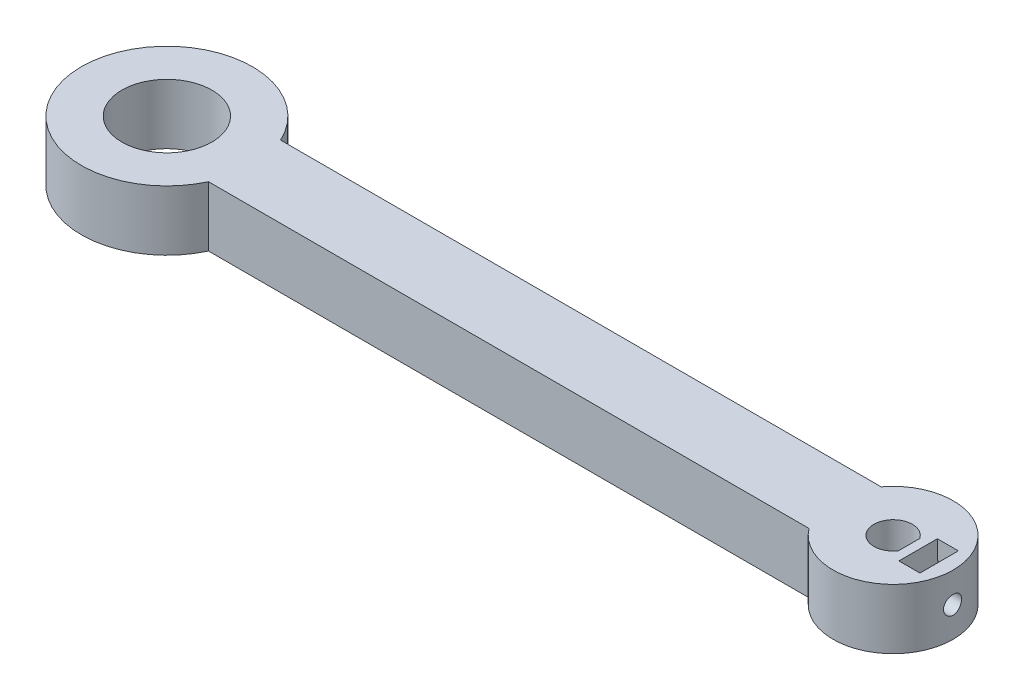
SolidWorks part; units mm, degrees
ref_plane "Plano frontal" through (0, 0, 0) normal (0, 0, 1) x (1, 0, 0)
ref_plane "Plano superior" through (0, 0, 0) normal (0, 1, 0) x (1, 0, 0)
ref_plane "Plano direito" through (0, 0, 0) normal (1, 0, 0) x (0, 0, -1)
sketch "Esboço1" plane through (0, 0, 0) normal (0, 1, 0) x (1, 0, 0)
  line L2 (12.9253, 6) -> (112.9253, 6)
  line L3 (12.9253, -6) -> (112.9253, -6)
  line L6 (-3.7598, 0) -> (4.2446, 0) construction
  line L8 (60.4626, 14.4945) -> (60.4626, -12.8649) construction
  arc A4 (12.9253, 6) -> (12.9253, -6) centre (0, 0) ccw
  arc A5 (112.9253, -6) -> (112.9253, 6) centre (120.9253, 0) ccw
  dimension "D2" = 28.5
  dimension "D3" = 20
  dimension "D4" = 100
  dimension "D7" = 6
  dimension "D8" = 6
extrude "Ressalto-extrusão1" add sketch "Esboço1" along normal blind 10
sketch "Esboço2" plane through (0, 10, 0) normal (0, 1, 0) x (1, 0, 0)
  line L0 (-11.6519, 0) -> (19.7902, 0) construction
  line L2 (123.592, 1.7688) -> (120.9253, 0) construction
  line L3 (120.9253, 0) -> (123.592, -1.7688) construction
  line L4 (60.4626, 11.203) -> (60.4626, -11.7589) construction
  line L5 (123.592, 1.7688) -> (123.592, -1.7688)
  line L6 (120.9253, -10) -> (120.9253, 0) construction
  line L7 (130.9253, 0) -> (118.3987, 0) construction
  arc A1 (123.592, -1.7688) -> (123.592, 1.7688) centre (120.9253, 0) cw
  circle A2 centre (0, 0) radius 7.5
  arc A3 (112.9253, -6) -> (112.9253, 6) centre (120.9253, 0) ccw construction
  dimension "D1" = 15
  dimension "D2" = 3.2
  dimension "D3" = 67.11
extrude "Corte-extrusão1" cut sketch "Esboço2" against normal up to surface (10 mm away) up to face at (60.6314, 0, 0)
sketch "Esboço4" plane through (123.592, 0, 0) normal (-1, 0, 0) x (0, 0, 1)
  line L0 (-1.7688, 0) -> (1.7688, 0) construction
  line L1 (1.7688, 0) -> (1.7688, 10) construction
  circle A0 centre (0, 5) radius 1.5
  point P5 (0, 0)
  point P8 (1.7688, 5)
  dimension "D1" = 3
extrude "Corte-extrusão3" cut sketch "Esboço4" against normal through all
sketch "Esboço5" plane through (0, 10, 0) normal (0, 1, 0) x (1, 0, 0)
  line L0 (133.1733, 0) -> (115.6294, 0) construction
  line L5 (58, 11.7245) -> (58, -11.1633) construction
  line L6 (128.592, -3.2) -> (125.092, -3.2)
  line L7 (125.092, 3.2) -> (125.092, -3.2)
  line L8 (128.592, 3.2) -> (128.592, -3.2)
  line L9 (128.592, 3.2) -> (125.092, 3.2)
  line L10 (123.592, -1.7688) -> (123.592, 1.7688) construction
  dimension "D1" = 3.5
  dimension "D2" = 6.4
  dimension "D3" = 3.2
  dimension "D4" = 1.5
extrude "Corte-extrusão4" cut sketch "Esboço5" against normal blind 5
sketch "Esboço7" plane through (123.592, 0, 0) normal (-1, 0, 0) x (0, 0, 1)
  line L0 (1.7688, 0) -> (1.7688, 10) construction
  line L1 (-0.0829, 8.695) -> (-3.2829, 6.8475)
  line L2 (-3.2829, 6.8475) -> (-3.2829, 3.1525)
  line L3 (-3.2829, 3.1525) -> (-0.0829, 1.305)
  line L4 (-0.0829, 1.305) -> (3.1171, 3.1525)
  line L5 (3.1171, 3.1525) -> (3.1171, 6.8475)
  line L6 (3.1171, 6.8475) -> (-0.0829, 8.695)
  line L7 (-1.7688, 0) -> (-1.7688, 10) construction
  circle A0 centre (-0.0829, 5) radius 3.2 construction
  point P10 (1.7688, 5)
  dimension "D1" = 6.4
extrude "Corte-extrusão6" cut sketch "Esboço7" against normal blind 3.5 from offset 1.5 offset against normal yes
